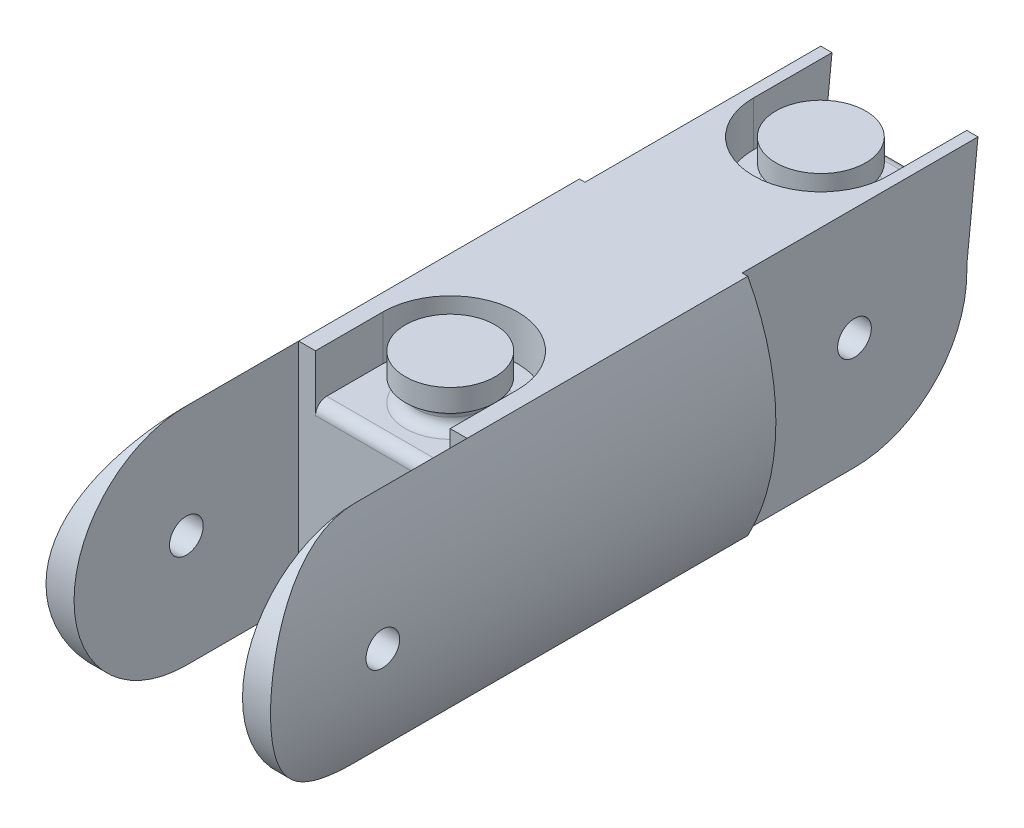
SolidWorks part; units mm, degrees
ref_plane "Alzado" through (0, 0, 0) normal (0, 0, 1) x (1, 0, 0)
ref_plane "Planta" through (0, 0, 0) normal (0, 1, 0) x (1, 0, 0)
ref_plane "Vista lateral" through (0, 0, 0) normal (1, 0, 0) x (0, 0, -1)
sketch "Croquis2" plane through (0, 0, 0) normal (0, 0, 1) x (1, 0, 0)
  line L5 (-7.5, -10) -> (7.5, -10)
  line L7 (-7.5, 10) -> (7.5, 10)
  line L9 (-7.5, -10) -> (7.5, 10) construction
  line L10 (-7.5, 10) -> (7.5, -10) construction
  arc A2 (-7.5, 10) -> (-7.5, -10) centre (11.25, 0) ccw
  arc A3 (7.5, -10) -> (7.5, 10) centre (-11.25, 0) ccw
  point P0 (0, 0)
  dimension "D1" = 15
  dimension "D2" = 20
extrude "Saliente-Extruir2" add sketch "Croquis2" along normal blind 45
sketch "Croquis4" plane through (0, 0, 0) normal (0, 0, -1) x (-1, 0, 0)
  line L1 (7.5, -10) -> (-7.5, -10) construction
  circle A0 centre (0, -7) radius 1.5
  dimension "D2" = 3
  dimension "D1" = 3
extrude "Cortar-Extruir1" cut sketch "Croquis4" against normal blind 50
sketch "Croquis3" plane through (0, 0, 0) normal (0, 0, -1) x (-1, 0, 0)
  line L8 (7.5, -10) -> (-7.5, -10) construction
  line L10 (7, 10) -> (7, -10)
  line L11 (7, -10) -> (3, -10)
  line L12 (-7, 10) -> (-7, -10)
  line L13 (7, 10) -> (-7, -10) construction
  line L14 (7, -10) -> (-7, 10) construction
  line L16 (3, -3) -> (3, -10)
  line L17 (-3, -10) -> (-7, -10)
  line L19 (-3, -3) -> (3, -3)
  line L20 (-3, -3) -> (-3, -10)
  line L21 (-7, 10) -> (7, 10)
  point P0 (0, 0)
  dimension "D1" = 14
  dimension "D2" = 4
  dimension "D3" = 4
  dimension "D4" = 7
extrude "Saliente-Extruir3" add sketch "Croquis3" along normal blind 20
sketch "Croquis8" plane through (-7, 0, 0) normal (-1, 0, 0) x (0, 0, 1)
  line L0 (-20, -10) -> (-20, 10) construction
  line L1 (-20, -10) -> (0, -10) construction
  circle A0 centre (-10, 0) radius 1.5
  point P4 (-20, 0)
  dimension "D1" = 3
  dimension "D2" = 10
  dimension "D3" = 10
extrude "Cortar-Extruir4" cut sketch "Croquis8" against normal blind 14
fillet "Redondeo1" radius 10 2 edges at (-5, -10, -20) (5, -10, -20)
sketch "Croquis6" plane through (0, 0, 45) normal (0, 0, 1) x (1, 0, 0)
  line L1 (-7.5, 10) -> (7.5, 10)
  line L2 (-7.5, 10) -> (-7.5, -10)
  line L3 (-7.5, -10) -> (7.5, -10)
  line L4 (7.5, 10) -> (7.5, -10)
extrude "Cortar-Extruir2" cut sketch "Croquis6" against normal blind 20
sketch "Croquis7" plane through (0, 0, 0) normal (1, 0, 0) x (0, 0, -1)
  line L0 (-45, 10) -> (-45, -10) construction
  line L2 (-35, -10) -> (-50, -10)
  line L4 (-35, 10) -> (-50, 10)
  line L5 (-50, -10) -> (-50, 10)
  arc A0 (-35, 10) -> (-35, -10) centre (-35, 0) ccw
  circle A1 centre (-35, 0) radius 1.5
  dimension "D3" = 10
  dimension "D4" = 3
  dimension "D1" = 10
  dimension "D2" = 15
  dimension "D5" = 20
extrude "Cortar-Extruir3" cut sketch "Croquis7" against normal through all both and the other way through all
sketch "Sketch1" plane through (0, 10, 0) normal (0, 1, 0) x (1, 0, 0)
  line L0 (-7, 20) -> (7, 20) construction
  line L1 (7.5, -25) -> (-7.5, -25) construction
  line L4 (-6, 14) -> (-6, 20)
  line L5 (-6, 20) -> (6, 20)
  line L6 (6, 14) -> (6, 20)
  line L8 (-6, -19) -> (-6, -25)
  line L9 (-6, -25) -> (6, -25)
  line L10 (6, -19) -> (6, -25)
  arc A0 (6, -19) -> (-6, -19) centre (0, -19) ccw
  arc A1 (-6, 14) -> (6, 14) centre (0, 14) ccw
  dimension "D3" = 12
  dimension "D4" = 12
  dimension "D1" = 6
  dimension "D2" = 6
extrude "Cut-Extrude1" cut sketch "Sketch1" against normal blind 4
sketch "Sketch2" plane through (0, 6, 0) normal (0, 1, 0) x (1, 0, 0)
  circle A0 centre (0, -19) radius 3
  circle A1 centre (0, 14) radius 3
  dimension "D1" = 6
  dimension "D2" = 6
extrude "Boss-Extrude1" add sketch "Sketch2" along normal blind 2
sketch "Sketch3" plane through (0, 8, 0) normal (0, 1, 0) x (1, 0, 0)
  circle A0 centre (0, -19) radius 4
  circle A1 centre (0, 14) radius 4
  dimension "D1" = 8
  dimension "D2" = 8
extrude "Boss-Extrude2" add sketch "Sketch3" along normal blind 2
fillet "Fillet2" radius 1 4 edges at (0, 8, -11) (0, 6, -11) (0, 8, 22) (0, 6, 22)
fillet "Fillet3" radius 1 2 edges at (0, 6, -20) (0, 6, 25)
fillet "Fillet4" radius 1 2 edges at (-1.5, -7, 0) (1.5, -7, 25)
sketch "Sketch4" plane through (7, 0, 0) normal (1, 0, 0) x (0, 0, -1)
  line L0 (20, 10) -> (21, 10)
  line L1 (21, 10) -> (19.6702, -2.5469)
  line L2 (19.6702, -2.5469) -> (20, 10)
  arc A0 (10, -10) -> (20, 0) centre (10, 0) ccw construction
  dimension "D1" = 1
sketch "Sketch5" plane through (-7, 0, 0) normal (-1, 0, 0) x (0, 0, 1)
  line L0 (-20, 10) -> (-21, 10)
  line L1 (-21, 10) -> (-19.6702, -2.5469)
  line L2 (-19.6702, -2.5469) -> (-20, 10)
extrude "Boss-Extrude3" add sketch "Sketch5" against normal blind 1
extrude "Boss-Extrude4" add sketch "Sketch4" against normal blind 1
